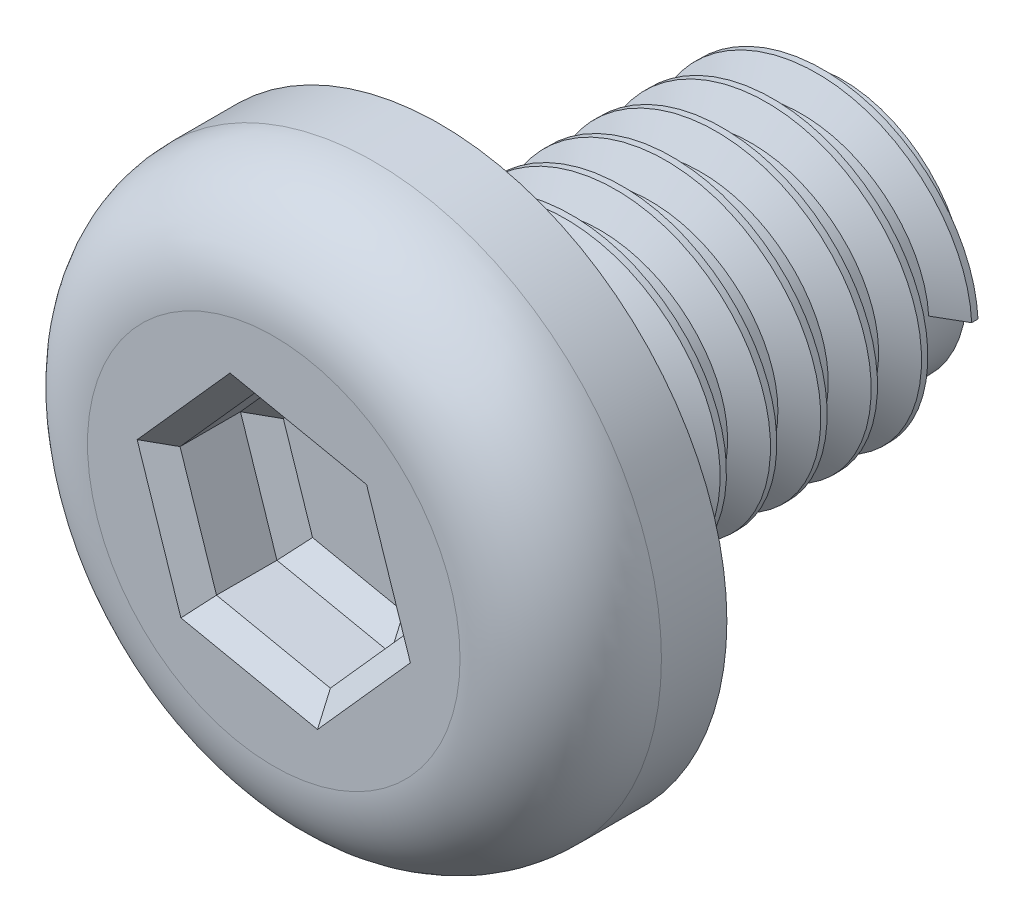
SolidWorks part; units mm, degrees
ref_plane "前视基准面" through (0, 0, 0) normal (0, 0, 1) x (1, 0, 0)
ref_plane "上视基准面" through (0, 0, 0) normal (0, 1, 0) x (1, 0, 0)
ref_plane "右视基准面" through (0, 0, 0) normal (1, 0, 0) x (0, 0, -1)
sketch "草图1" plane through (0, 0, 0) normal (0, 0, 1) x (1, 0, 0)
  circle A0 centre (0, 0) radius 2.85
  dimension "D1" = 5.7
extrude "凸台-拉伸1" add sketch "草图1" along normal blind 1.65
sketch "草图2" plane through (0, 0, 0) normal (0, 0, -1) x (-1, 0, 0)
  circle A0 centre (0, 0) radius 1.2295
  dimension "D1" = 2.459
extrude "凸台-拉伸2" add sketch "草图2" along normal blind 4
fillet "圆角1" radius 1 1 edges at (2.85, 0, 1.65)
sketch "草图3" plane through (0, 0, 1.65) normal (0, 0, 1) x (1, 0, 0)
  line L1 (0.3622, -1.0964) -> (1.1306, -0.2345)
  line L2 (1.1306, -0.2345) -> (0.7684, 0.8619)
  line L3 (0.7684, 0.8619) -> (-0.3622, 1.0964)
  line L4 (-0.3622, 1.0964) -> (-1.1306, 0.2345)
  line L5 (-1.1306, 0.2345) -> (-0.7684, -0.8619)
  line L6 (-0.7684, -0.8619) -> (0.3622, -1.0964)
  circle A0 centre (0, 0) radius 1 construction
  dimension "D1" = 2
extrude "切除-拉伸1" cut sketch "草图3" against normal blind 1
chamfer "倒角1" distance 0.2 angle 45 12 edges at (0.7464, -0.6655, 1.65) (0.9495, 0.3137, 1.65) (0.2031, 0.9792, 1.65) (-0.7464, 0.6655, 1.65) (-0.9495, -0.3137, 1.65) (-0.2031, -0.9792, 1.65) (-0.9495, -0.3137, 0.65) (-0.7464, 0.6655, 0.65) (0.2031, 0.9792, 0.65) (0.9495, 0.3137, 0.65) (0.7464, -0.6655, 0.65) (-0.2031, -0.9792, 0.65)
thread "螺纹线1" pitch 0.5 method extrude profile "螺纹线轮廓2" start angle 0, offset 0, length 0, pitch 0.5, diameter 2.459
ref_plane "基准面2" through (1.2295, 0, -4) normal (0, -1, 0) x (1, 0, 0)
sketch "螺纹线轮廓2" plane through (1.2295, 0, -4) normal (0, -1, 0) x (1, 0, 0)
  line L0 (0, 0) -> (0, 0.5) construction
  line L1 (0, 0) -> (0.2706, 0.1562)
  line L2 (0.2706, 0.1562) -> (0.2706, 0.2187)
  line L3 (0.2706, 0.2187) -> (0, 0.375)
  line L4 (0.2706, 0.1875) -> (0, 0.1875) construction
  line L11 (0, 0) -> (0, 0.375)
  point P2 (0, 0)
  dimension "Pitch" = 0.5
  dimension "Profile_Angle" = 60
  dimension "Profile_Land" = 0.0625
  dimension "Profile_Height" = 0.2706
